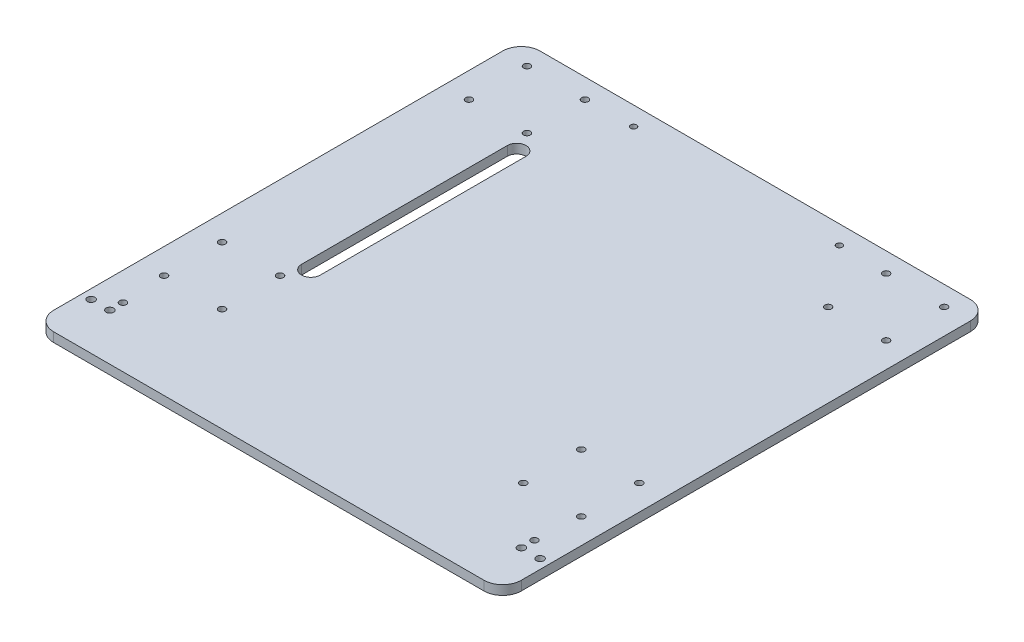
SolidWorks part; units mm, degrees
ref_plane "前视基准面" through (0, 0, 0) normal (0, 0, 1) x (1, 0, 0)
ref_plane "上视基准面" through (0, 0, 0) normal (0, 1, 0) x (1, 0, 0)
ref_plane "右视基准面" through (0, 0, 0) normal (1, 0, 0) x (0, 0, -1)
sketch "草图1" plane through (0, 0, 0) normal (0, 1, 0) x (1, 0, 0)
  line L0 (-125, 83) -> (-75, 83) construction
  line L1 (-125, -130) -> (125, -130)
  line L2 (-125, -130) -> (-125, 130)
  line L3 (-125, 130) -> (125, 130)
  line L4 (125, -130) -> (125, 130)
  line L5 (-125, -130) -> (125, 130) construction
  line L6 (-125, 130) -> (125, -130) construction
  line L7 (-125, -80) -> (-75, -80) construction
  line L8 (-125, -80) -> (-125, -38) construction
  line L9 (-125, -38) -> (-75, -38) construction
  line L10 (-75, -80) -> (-75, -38) construction
  line L11 (-117, -80) -> (-75, -80) construction
  line L12 (-117, -80) -> (-117, -38) construction
  line L13 (-117, -38) -> (-75, -38) construction
  line L14 (-75, -80) -> (-75, -38) construction
  line L15 (-117, -80) -> (-75, -38) construction
  line L16 (-117, -38) -> (-75, -80) construction
  line L17 (-111.5, -43.5) -> (-80.5, -43.5) construction
  line L18 (-111.5, -43.5) -> (-111.5, -74.5) construction
  line L19 (-111.5, -74.5) -> (-80.5, -74.5) construction
  line L20 (-80.5, -43.5) -> (-80.5, -74.5) construction
  line L21 (-125, 83) -> (-125, 125) construction
  line L22 (-125, 125) -> (-75, 125) construction
  line L23 (-75, 83) -> (-75, 125) construction
  line L24 (-117, 83) -> (-75, 83) construction
  line L25 (-117, 83) -> (-117, 125) construction
  line L26 (-117, 125) -> (-75, 125) construction
  line L27 (-75, 83) -> (-75, 125) construction
  line L28 (-117, 83) -> (-75, 125) construction
  line L29 (-117, 125) -> (-75, 83) construction
  line L30 (-111.5, 119.5) -> (-80.5, 119.5) construction
  line L31 (-111.5, 119.5) -> (-111.5, 88.5) construction
  line L32 (-111.5, 88.5) -> (-80.5, 88.5) construction
  line L33 (-80.5, 119.5) -> (-80.5, 88.5) construction
  line L34 (0, -130) -> (0, 130) construction
  line L35 (80.5, -43.5) -> (80.5, -74.5) construction
  line L36 (111.5, -74.5) -> (80.5, -74.5) construction
  line L37 (111.5, -43.5) -> (111.5, -74.5) construction
  line L38 (111.5, -43.5) -> (80.5, -43.5) construction
  line L39 (117, -38) -> (75, -80) construction
  line L40 (117, -80) -> (75, -38) construction
  line L41 (75, -80) -> (75, -38) construction
  line L42 (117, -38) -> (75, -38) construction
  line L43 (117, -80) -> (117, -38) construction
  line L44 (117, -80) -> (75, -80) construction
  line L45 (75, -80) -> (75, -38) construction
  line L46 (125, -38) -> (75, -38) construction
  line L47 (125, -80) -> (125, -38) construction
  line L48 (125, -80) -> (75, -80) construction
  line L49 (80.5, 119.5) -> (80.5, 88.5) construction
  line L50 (111.5, 88.5) -> (80.5, 88.5) construction
  line L51 (111.5, 119.5) -> (111.5, 88.5) construction
  line L52 (111.5, 119.5) -> (80.5, 119.5) construction
  line L53 (117, 125) -> (75, 83) construction
  line L54 (117, 83) -> (75, 125) construction
  line L55 (75, 83) -> (75, 125) construction
  line L56 (117, 125) -> (75, 125) construction
  line L57 (117, 83) -> (117, 125) construction
  line L58 (117, 83) -> (75, 83) construction
  line L59 (75, 83) -> (75, 125) construction
  line L60 (125, 125) -> (75, 125) construction
  line L61 (125, 83) -> (125, 125) construction
  line L62 (125, 83) -> (75, 83) construction
  line L63 (-75, 77.5) -> (-75, -32.5) construction
  line L64 (-70, 77.5) -> (-70, -32.5)
  line L65 (-80, 77.5) -> (-80, -32.5)
  circle A0 centre (-111.5, 119.5) radius 1.8
  circle A1 centre (-80.5, 119.5) radius 1.8
  circle A2 centre (-80.5, 88.5) radius 1.8
  circle A3 centre (-111.5, 88.5) radius 1.8
  circle A4 centre (-111.5, -43.5) radius 1.8
  circle A5 centre (-80.5, -43.5) radius 1.8
  circle A6 centre (-80.5, -74.5) radius 1.8
  circle A7 centre (-111.5, -74.5) radius 1.8
  circle A8 centre (111.5, -74.5) radius 1.8
  circle A9 centre (80.5, -74.5) radius 1.8
  circle A10 centre (80.5, -43.5) radius 1.8
  circle A11 centre (111.5, -43.5) radius 1.8
  circle A12 centre (111.5, 88.5) radius 1.8
  circle A13 centre (80.5, 88.5) radius 1.8
  circle A14 centre (80.5, 119.5) radius 1.8
  circle A15 centre (111.5, 119.5) radius 1.8
  circle A16 centre (-120, -105) radius 2
  circle A17 centre (-110, -105) radius 2
  circle A18 centre (110, -105) radius 2
  circle A19 centre (120, -105) radius 2
  circle A20 centre (-55, 120) radius 1.6
  circle A21 centre (55, 120) radius 1.6
  arc A22 (-70, 77.5) -> (-80, 77.5) centre (-75, 77.5) ccw
  circle A23 centre (-110, -98) radius 1.8
  arc A24 (-80, -32.5) -> (-70, -32.5) centre (-75, -32.5) ccw
  circle A25 centre (110, -98) radius 1.8
  point P0 (0, 0)
  point P10 (-96, -59)
  point P22 (-96, 104)
  point P38 (-96, 104)
  point P45 (-96, -59)
  point P58 (96, -59)
  point P73 (96, 104)
  point P89 (-75, 22.5)
  dimension "D14" = 3.6
  dimension "D15" = 3.6
  dimension "D9" = 10
  dimension "D17" = 4
  dimension "D18" = 4
  dimension "D22" = 10
  dimension "D23" = 3.2
  dimension "D21" = 55
  dimension "D24" = 3.6
  dimension "D25" = 15
  dimension "D26" = 18
  dimension "D28" = 5
  dimension "D1" = 250
  dimension "D2" = 260
  dimension "D3" = 50
  dimension "D4" = 5
  dimension "D5" = 42
  dimension "D6" = 31
  dimension "D7" = 50
  dimension "D8" = 42
  dimension "D10" = 31
  dimension "D11" = 50
  dimension "D12" = 5
  dimension "D19" = 25
  dimension "D20" = 25
  dimension "D27" = 50
  dimension "D29" = 110
  dimension "D30" = 52.5
  dimension "D13" = 4
  dimension "D16" = 4
extrude "凸台-拉伸1" add sketch "草图1" along normal blind 5
fillet "圆角2" radius 10 4 edges at (125, 2.5, -130) (125, 2.5, 130) (-125, 2.5, -130) (-125, 2.5, 130)
